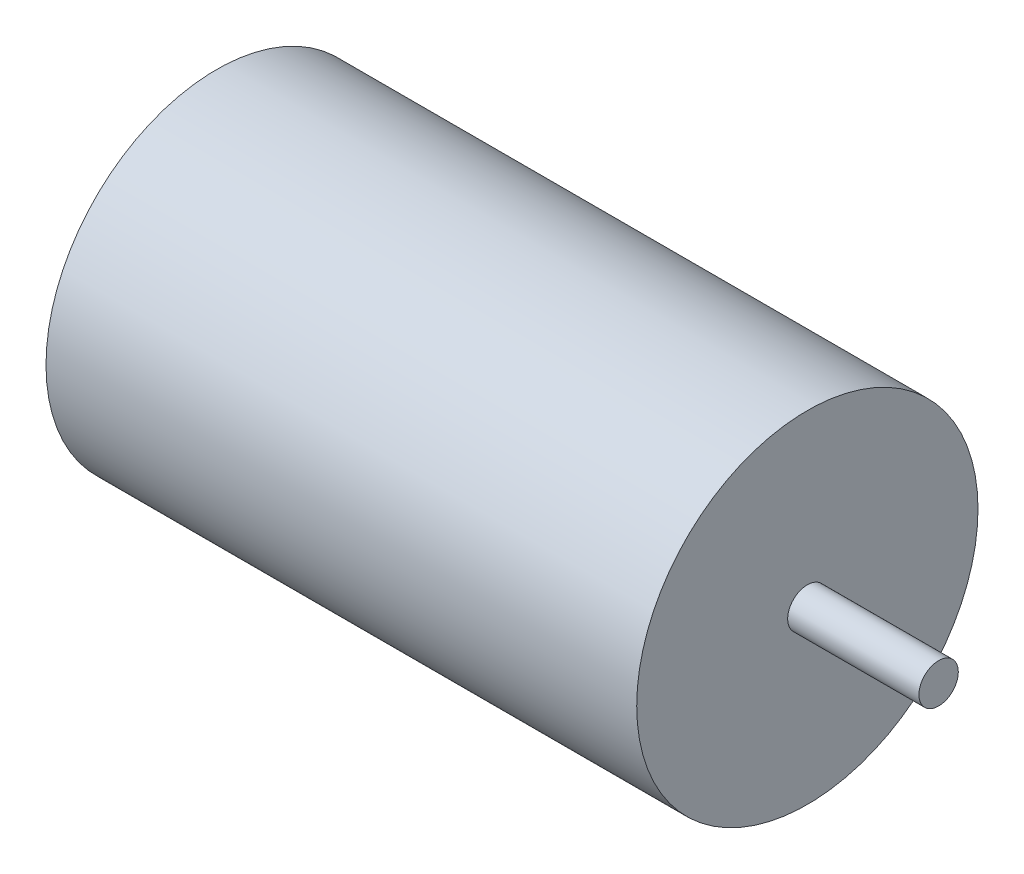
SolidWorks part; units mm, degrees
ref_plane "Front Plane" through (0, 0, 0) normal (1, 0, 0) x (0, 1, 0)
ref_plane "Top Plane" through (0, 0, 0) normal (0, 0, 1) x (0, 1, 0)
ref_plane "Right Plane" through (0, 0, 0) normal (0, 1, 0) x (-1, 0, 0)
sketch "Sketch1" plane through (0, 0, 0) normal (1, 0, 0) x (0, 1, 0)
  circle A0 centre (0, 0) radius 13
  circle A1 centre (0, 0) radius 1.5
  dimension "D1" = 26
  dimension "D2" = 3
extrude "Boss-Extrude1" add sketch "Sketch1" along normal blind 10 contours A1 region at (0, 0, 0)
extrude "Boss-Extrude2" add sketch "Sketch1<3>" against normal blind 45 contours A1 | A0 A1 region at (0, -12.6323, 0) region at (0, 0, 0)
sketch "Sketch1<3>" plane through (0, 0, 0) normal (1, 0, 0) x (0, 1, 0) same geometry as "Sketch1"
